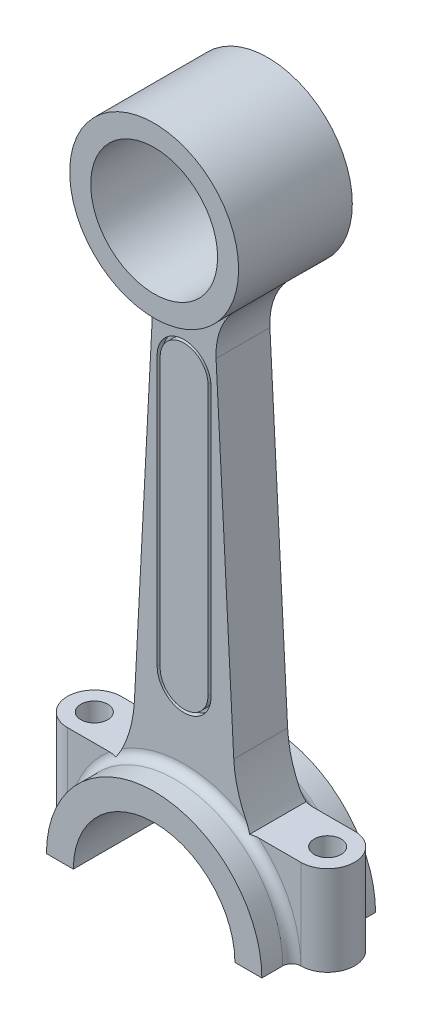
SolidWorks part; units mm, degrees
ref_plane "Front Plane" through (0, 0, 0) normal (0, 0, 1) x (1, 0, 0)
ref_plane "Top Plane" through (0, 0, 0) normal (0, 1, 0) x (1, 0, 0)
ref_plane "Right Plane" through (0, 0, 0) normal (1, 0, 0) x (0, 0, -1)
sketch "Sketch1" plane through (0, 0, 0) normal (0, 0, 1) x (1, 0, 0)
  line L0 (0, 201.2) -> (0, 0) construction
  line L1 (-63.9056, 0) -> (85.9683, 0) construction
  line L2 (-36, 0) -> (-27, 0)
  line L3 (27, 0) -> (36, 0)
  circle A0 centre (0, 201.2) radius 21.206
  circle A1 centre (0, 201.2) radius 28.2328
  arc A2 (27, 0) -> (-27, 0) centre (0, 0) ccw
  arc A3 (36, 0) -> (-36, 0) centre (0, 0) ccw
  dimension "D1" = 201.2
  dimension "D4" = 27
  dimension "D5" = 36
  dimension "D2" = 0
  dimension "D3" = 0
extrude "Boss-Extrude1" add sketch "Sketch1" along normal mid plane 38
sketch "Sketch2" plane through (0, 0, 0) normal (0, 0, 1) x (1, 0, 0)
  line L0 (-10, 174.7975) -> (-17.5123, 31.4534)
  line L1 (0, -150.191) -> (0, 148.2155) construction
  line L2 (10, 174.7975) -> (17.5123, 31.4534)
  circle A0 centre (0, 201.2) radius 28.2328 construction
  circle A1 centre (0, 0) radius 36 construction
  arc A2 (-10, 174.7975) -> (10, 174.7975) centre (0, 201.2) ccw
  arc A3 (17.5123, 31.4534) -> (-17.5123, 31.4534) centre (0, 0) ccw
  point P12 (-9.5647, 75.3625)
  point P13 (-18.2263, -54.2957)
  point P14 (15.7498, -53.29)
  point P15 (6.9894, 74.5719)
  point P16 (14.3818, -52.806)
  point P17 (0, 0)
  point P18 (0, 0)
  dimension "D1" = 6
  dimension "D2" = 20
extrude "Boss-Extrude2" add sketch "Sketch2" along normal mid plane 18 contours L1 A3 L2 A2 | A3 L1 A2 L0 region at (0, 171.4915, 0)
fillet "Fillet1" radius 22.5 2 edges at (10, 174.7975, 0) (-10, 174.7975, 0)
fillet "Fillet2" radius 40 2 edges at (17.5123, 31.4534, 0) (-17.5123, 31.4534, 0)
sketch "Sketch3" plane through (0, 0, 9) normal (0, 0, 1) x (1, 0, 0)
  line L0 (0, 152.7714) -> (0, 62.7714) construction
  line L1 (8, 152.7714) -> (8, 62.7714)
  line L2 (-8, 152.7714) -> (-8, 62.7714)
  arc A0 (8, 152.7714) -> (-8, 152.7714) centre (0, 152.7714) ccw
  arc A1 (-8, 62.7714) -> (8, 62.7714) centre (0, 62.7714) ccw
  point P3 (0, 107.7714)
  point P8 (0, 0)
  dimension "D1" = 90
  dimension "D2" = 16
extrude "Cut-Extrude-Thin1" cut sketch "Sketch3" against normal mid plane 4 thin thin type one direction wall 1
sketch "Sketch4" plane through (0, 0, 0) normal (0, 1, 0) x (1, 0, 0)
  line L0 (-39, 0) -> (39, 0) construction
  line L1 (-39, 9) -> (39, 9)
  line L2 (-39, -9) -> (39, -9)
  arc A0 (-39, 9) -> (-39, -9) centre (-39, 0) ccw
  arc A1 (39, -9) -> (39, 9) centre (39, 0) ccw
  point P3 (0, 0)
  dimension "D1" = 9
  dimension "D2" = 78
  dimension "D3" = 39
extrude "Boss-Extrude3" add sketch "Sketch4" along normal blind 30
sketch "Sketch5" plane through (0, 30, 0) normal (0, 1, 0) x (1, 0, 0)
  circle A0 centre (-39, 0) radius 4.5
  circle A1 centre (39, 0) radius 4.5
extrude "Cut-Extrude1" cut sketch "Sketch5" against normal blind 30
sketch "Sketch7" plane through (0, 0, 9) normal (0, 0, 1) x (1, 0, 0)
  line L0 (-27, 0) -> (27, 0) construction
  line L1 (-27, 0) -> (27, 0)
  arc A0 (27, 0) -> (-27, 0) centre (0, 0) ccw construction
  arc A1 (27, 0) -> (-27, 0) centre (0, 0) ccw
extrude "Cut-Extrude2" cut sketch "Sketch7" against normal blind 30
fillet "Fillet3" radius 3 2 edges at (0, 36, -9) (0, 36, 9)
